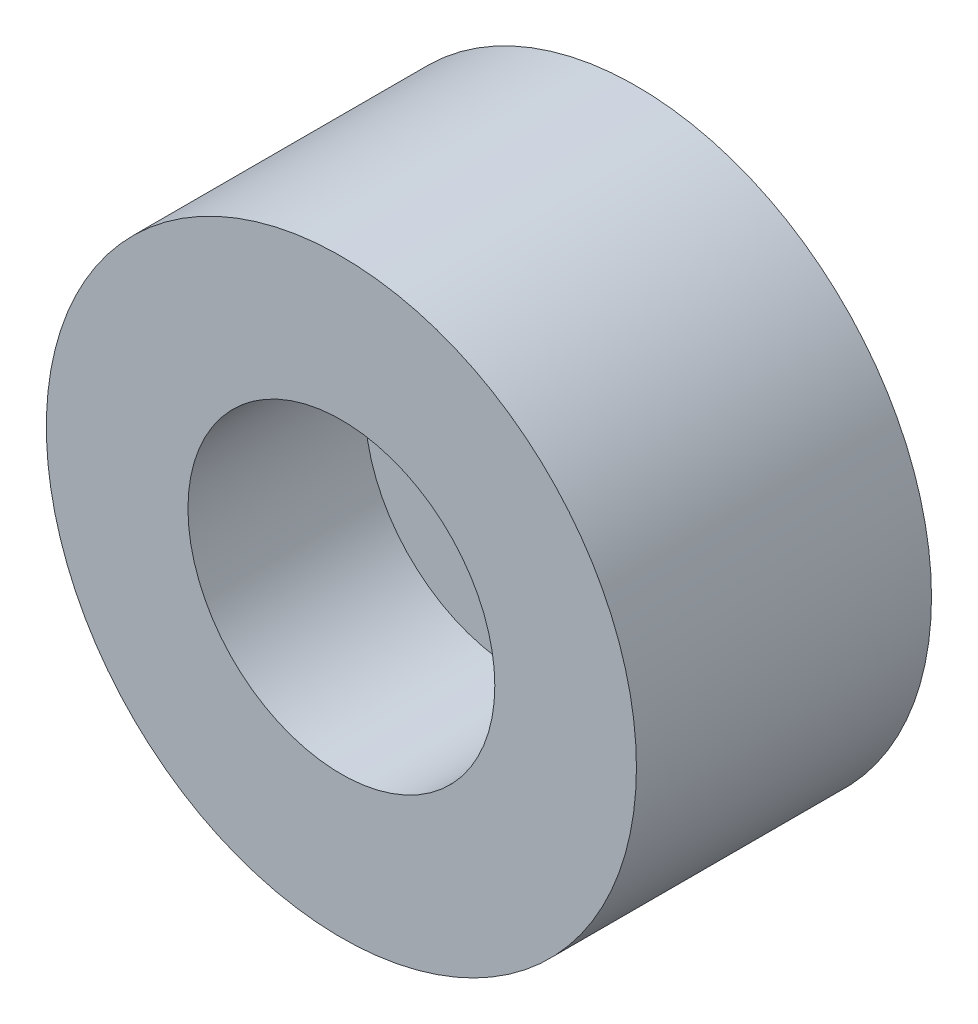
SolidWorks part; units mm, degrees
ref_plane "Front" through (0, 0, 0) normal (0, 0, 1) x (1, 0, 0)
ref_plane "Top" through (0, 0, 0) normal (0, 1, 0) x (1, 0, 0)
ref_plane "Right" through (0, 0, 0) normal (1, 0, 0) x (0, 0, -1)
sketch "Sketch1" plane through (0, 0, 0) normal (0, 0, 1) x (1, 0, 0)
  circle A0 centre (0, 0) radius 6.604
  circle A1 centre (0, 0) radius 12.7
  dimension "D1" = 13.208
  dimension "D2" = 25.4
extrude "Boss-Extrude1" add sketch "Sketch1" along normal blind 12.7
extrude "Boss-Extrude2" add sketch "Sketch1<2>" along normal blind 5.08 contours A0 region at (0, 0, 0)
sketch "Sketch1<2>" plane through (0, 0, 0) normal (0, 0, 1) x (1, 0, 0) same geometry as "Sketch1"
